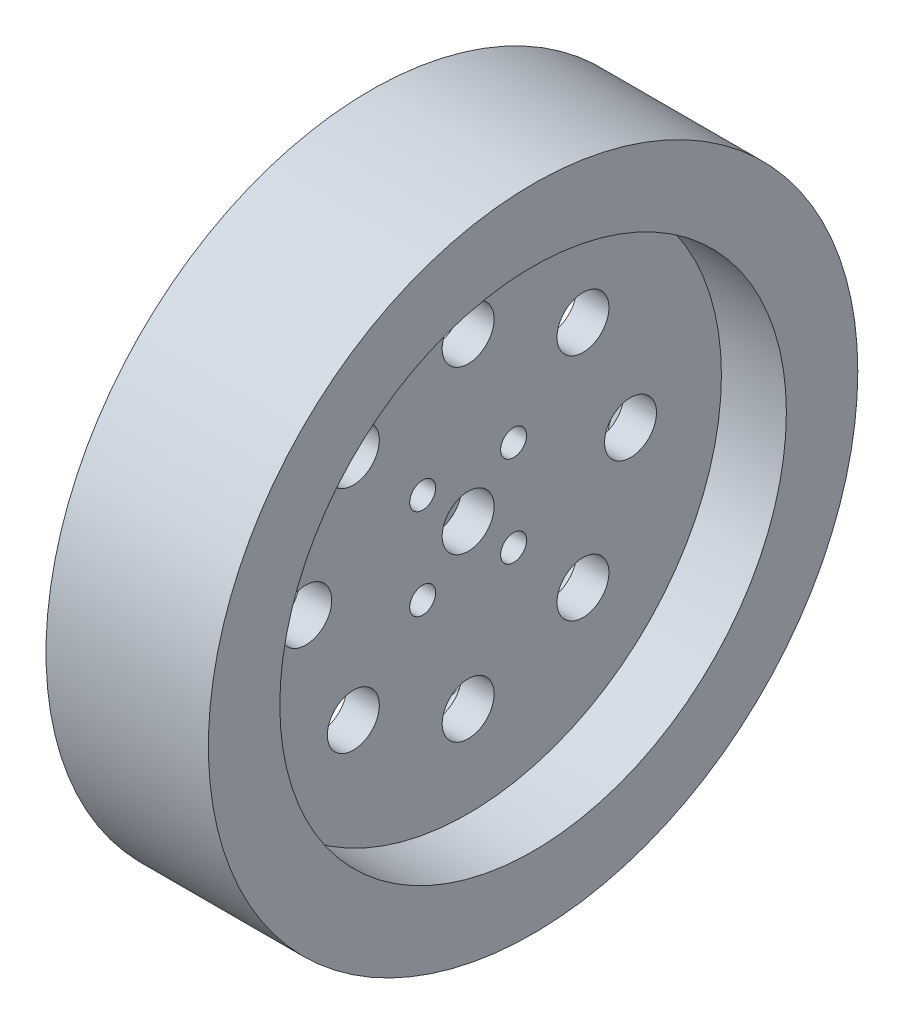
SolidWorks part; units mm, degrees
ref_plane "Front Plane" through (0, 0, 0) normal (0, 0, 1) x (1, 0, 0)
ref_plane "Top Plane" through (0, 0, 0) normal (0, 1, 0) x (1, 0, 0)
ref_plane "Right Plane" through (0, 0, 0) normal (1, 0, 0) x (0, 0, -1)
sketch "Esquisse1" plane through (0, 0, 0) normal (1, 0, 0) x (0, 0, -1)
  circle A0 centre (0, 0) radius 50
  dimension "D1" = 100
extrude "Boss.-Extru.1" add sketch "Esquisse1" along normal blind 12.5
ref_plane "Plan_Ext" through (12.5, 0, 0) normal (1, 0, 0) x (0, 0, -1)
sketch "Esquisse3" plane through (12.5, 0, 0) normal (1, 0, 0) x (0, 0, -1)
  circle A0 centre (0, 0) radius 39
  dimension "D1" = 78
extrude "Enlèv. mat.-Extru.2" cut sketch "Esquisse3" against normal blind 10
ref_plane "Plan_Int" through (2.5, 0, 0) normal (1, 0, 0) x (0, 0, -1)
sketch "Esquisse4" plane through (2.5, 0, 0) normal (1, 0, 0) x (0, 0, -1)
  circle A0 centre (0, 25) radius 4
  dimension "D1" = 8
  dimension "D2" = 25
extrude "Enlèv. mat.-Extru.3" cut sketch "Esquisse4" against normal through all
ref_axis "Axe1" through (0, 0, 0) along (1, 0, 0)
pattern_circular "Répétition circulaire1" count 8 over 360 about axis through (0, 0, 0) along (1, 0, 0) of "Enlèv. mat.-Extru.3"
sketch "Esquisse5" plane through (2.5, 0, 0) normal (1, 0, 0) x (0, 0, -1)
  circle A0 centre (0, 0) radius 4
  dimension "D1" = 8
extrude "Enlèv. mat.-Extru.4" cut sketch "Esquisse5" against normal through all
sketch "Esquisse6" plane through (2.5, 0, 0) normal (1, 0, 0) x (0, 0, -1)
  circle A0 centre (-7, 7) radius 2
  point P2 (0, 0)
  point P5 (11.6769, 3.2791)
  dimension "D1" = 7
  dimension "D3" = 4
  dimension "D2" = 7
extrude "Enlèv. mat.-Extru.5" cut sketch "Esquisse6" against normal through all
pattern_circular "Répétition circulaire2" count 4 over 360 about axis through (0, 0, 0) along (1, 0, 0) of "Enlèv. mat.-Extru.5"
mirror "Symétrie2" about plane through (0, 0, 0) normal (1, 0, 0) of "Répétition circulaire2", "Enlèv. mat.-Extru.5", "Enlèv. mat.-Extru.4", "Répétition circulaire1", "Enlèv. mat.-Extru.3", "Enlèv. mat.-Extru.2", "Boss.-Extru.1"
ref_plane "Plan1" through (-2.5, 0, 0) normal (-1, 0, 0) x (0, 0, 1)
sketch "Esquisse7" plane through (-2.5, 0, 0) normal (-1, 0, 0) x (0, 0, 1)
  circle A0 centre (0, 0) radius 12.5
  dimension "D1" = 25
extrude "Boss.-Extru.2" add sketch "Esquisse7" along normal blind 8 contours A0
